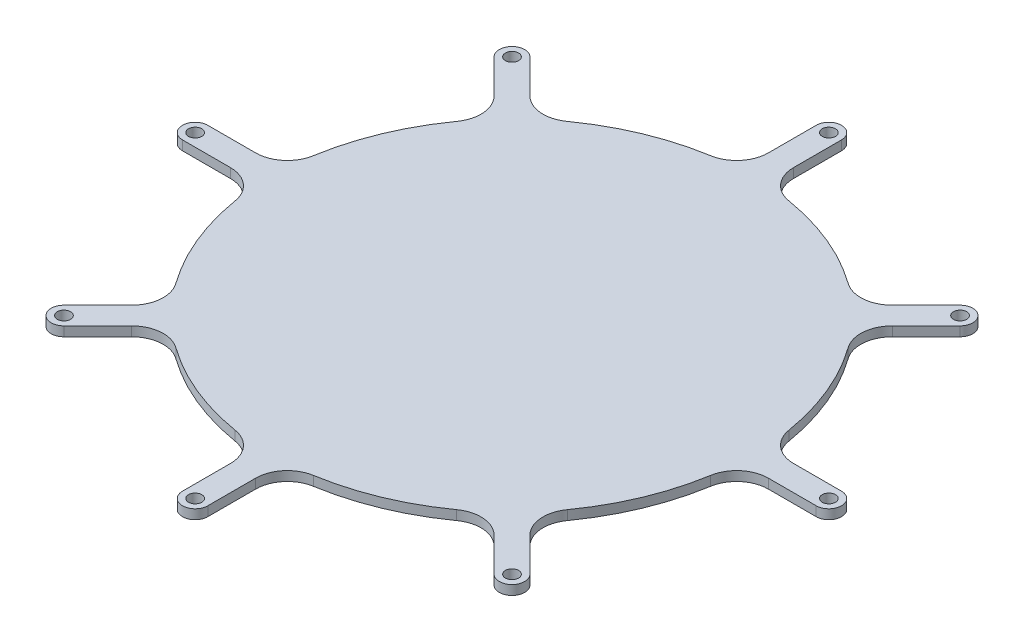
SolidWorks part; units mm, degrees
material "Thornel Mat VMA"
ref_plane "Front Plane" through (0, 0, 0) normal (0, 0, 1) x (1, 0, 0)
ref_plane "Top Plane" through (0, 0, 0) normal (0, 1, 0) x (1, 0, 0)
ref_plane "Right Plane" through (0, 0, 0) normal (1, 0, 0) x (0, 0, -1)
sketch "Sketch1" plane through (0, 0, 0) normal (0, 1, 0) x (1, 0, 0)
  line L0 (0, 0) -> (100.17, 0) construction
  line L1 (36.7402, 0) -> (100.17, 0) construction
  line L2 (36.7402, 4) -> (100.17, 4)
  line L3 (36.7402, -4) -> (100.17, -4)
  line L4 (25.9793, -25.9793) -> (70.8309, -70.8309) construction
  line L5 (28.8077, -23.1508) -> (73.6593, -68.0025)
  line L6 (23.1508, -28.8077) -> (68.0025, -73.6593)
  line L7 (0, -36.7402) -> (0, -100.17) construction
  line L8 (4, -36.7402) -> (4, -100.17)
  line L9 (-4, -36.7402) -> (-4, -100.17)
  line L10 (-25.9793, -25.9793) -> (-70.8309, -70.8309) construction
  line L11 (-23.1508, -28.8077) -> (-68.0025, -73.6593)
  line L12 (-28.8077, -23.1508) -> (-73.6593, -68.0025)
  line L13 (-36.7402, 0) -> (-100.17, 0) construction
  line L14 (-36.7402, -4) -> (-100.17, -4)
  line L15 (-36.7402, 4) -> (-100.17, 4)
  line L16 (-25.9793, 25.9793) -> (-70.8309, 70.8309) construction
  line L17 (-28.8077, 23.1508) -> (-73.6593, 68.0025)
  line L18 (-23.1508, 28.8077) -> (-68.0025, 73.6593)
  line L19 (0, 36.7402) -> (0, 100.17) construction
  line L20 (-4, 36.7402) -> (-4, 100.17)
  line L21 (4, 36.7402) -> (4, 100.17)
  line L22 (25.9793, 25.9793) -> (70.8309, 70.8309) construction
  line L23 (23.1508, 28.8077) -> (68.0025, 73.6593)
  line L24 (28.8077, 23.1508) -> (73.6593, 68.0025)
  circle A0 centre (0, 0) radius 76.17
  arc A1 (36.7402, 4) -> (36.7402, -4) centre (36.7402, 0) ccw
  arc A2 (100.17, -4) -> (100.17, 4) centre (100.17, 0) ccw
  arc A3 (28.8077, -23.1508) -> (23.1508, -28.8077) centre (25.9793, -25.9793) ccw
  arc A4 (68.0025, -73.6593) -> (73.6593, -68.0025) centre (70.8309, -70.8309) ccw
  arc A5 (4, -36.7402) -> (-4, -36.7402) centre (0, -36.7402) ccw
  arc A6 (-4, -100.17) -> (4, -100.17) centre (0, -100.17) ccw
  arc A7 (-23.1508, -28.8077) -> (-28.8077, -23.1508) centre (-25.9793, -25.9793) ccw
  arc A8 (-73.6593, -68.0025) -> (-68.0025, -73.6593) centre (-70.8309, -70.8309) ccw
  arc A9 (-36.7402, -4) -> (-36.7402, 4) centre (-36.7402, 0) ccw
  arc A10 (-100.17, 4) -> (-100.17, -4) centre (-100.17, 0) ccw
  arc A11 (-28.8077, 23.1508) -> (-23.1508, 28.8077) centre (-25.9793, 25.9793) ccw
  arc A12 (-68.0025, 73.6593) -> (-73.6593, 68.0025) centre (-70.8309, 70.8309) ccw
  arc A13 (-4, 36.7402) -> (4, 36.7402) centre (0, 36.7402) ccw
  arc A14 (4, 100.17) -> (-4, 100.17) centre (0, 100.17) ccw
  arc A15 (23.1508, 28.8077) -> (28.8077, 23.1508) centre (25.9793, 25.9793) ccw
  arc A16 (73.6593, 68.0025) -> (68.0025, 73.6593) centre (70.8309, 70.8309) ccw
  point P5 (68.4551, 0)
  point P14 (48.4051, -48.4051)
  point P21 (0, -68.4551)
  point P28 (-48.4051, -48.4051)
  point P35 (-68.4551, 0)
  point P42 (-48.4051, 48.4051)
  point P49 (0, 68.4551)
  point P56 (48.4051, 48.4051)
  point P61 (0, 0)
  dimension "D1" = 152.34
  dimension "D3" = 4
  dimension "D2" = 100.17
  dimension "D4" = 8
extrude "Boss-Extrude1" add sketch "Sketch1" along normal blind 3 contours A15 L23 A0 L21 A13 L20 L18 A11 L17 L15 A9 L14 L12 A7 L11 L9 A5 L8 L6 A3 L5 L3 A1 L2 L24 | L21 A14 L20 A0 | L20 A13 L21 A0 | L18 A12 L17 A0 | L17 A11 L18 A0 | L15 A10 L14 A0 | L14 A9 L15 A0 | L12 A8 L11 A0 | L11 A7 L12 A0 | L8 A5 L9 A0 | L9 A6 L8 A0 | L5 A3 L6 A0 | L6 A4 L5 A0 | L2 A1 L3 A0 | L3 A2 L2 A0 | L23 A15 L24 A0 | L24 A16 L23 A0 region at (0, 0, 0) region at (54.8575, 0, 0) region at (89.7379, 0, 0) region at (63.4543, 0, -63.4543) region at (38.7901, 0, -38.7901) region at (38.7901, 0, 38.7901) region at (63.4543, 0, 63.4543) region at (0, 0, -89.7379) region at (0, 0, -54.8575) region at (0, 0, 54.8575) region at (0, 0, 89.7379) region at (-63.4543, 0, -63.4543) region at (-38.7901, 0, -38.7901) region at (-38.7901, 0, 38.7901) region at (-63.4543, 0, 63.4543) region at (-89.7379, 0, 0) region at (-54.8575, 0, 0)
sketch "Sketch3" plane through (0, 3, 0) normal (0, 1, 0) x (1, 0, 0)
  circle A0 centre (0, 0) radius 100.17 construction
  circle A1 centre (100.17, 0) radius 2.1
  circle A2 centre (70.8309, -70.8309) radius 2.1
  circle A3 centre (0, -100.17) radius 2.1
  circle A4 centre (-70.8309, -70.8309) radius 2.1
  circle A5 centre (-100.17, 0) radius 2.1
  circle A6 centre (-70.8309, 70.8309) radius 2.1
  circle A7 centre (0, 100.17) radius 2.1
  circle A8 centre (70.8309, 70.8309) radius 2.1
  point P6 (0, 0)
  point P22 (0, 0)
  dimension "D1" = 4.2
  dimension "D2" = 8
extrude "Cut-Extrude1" cut sketch "Sketch3" against normal blind 5
fillet "Fillet1" radius 10 16 edges at (50.9576, 1.5, 56.6144) (-4, 1.5, 76.0649) (-56.6144, 1.5, 50.9576) (-76.0649, 1.5, 4) (-56.6144, 1.5, -50.9576) (-4, 1.5, -76.0649) (-76.0649, 1.5, -4) (-50.9576, 1.5, -56.6144) (50.9576, 1.5, -56.6144) (4, 1.5, -76.0649) (76.0649, 1.5, -4) (56.6144, 1.5, -50.9576) (76.0649, 1.5, 4) (56.6144, 1.5, 50.9576) (4, 1.5, 76.0649) (-50.9576, 1.5, 56.6144)
